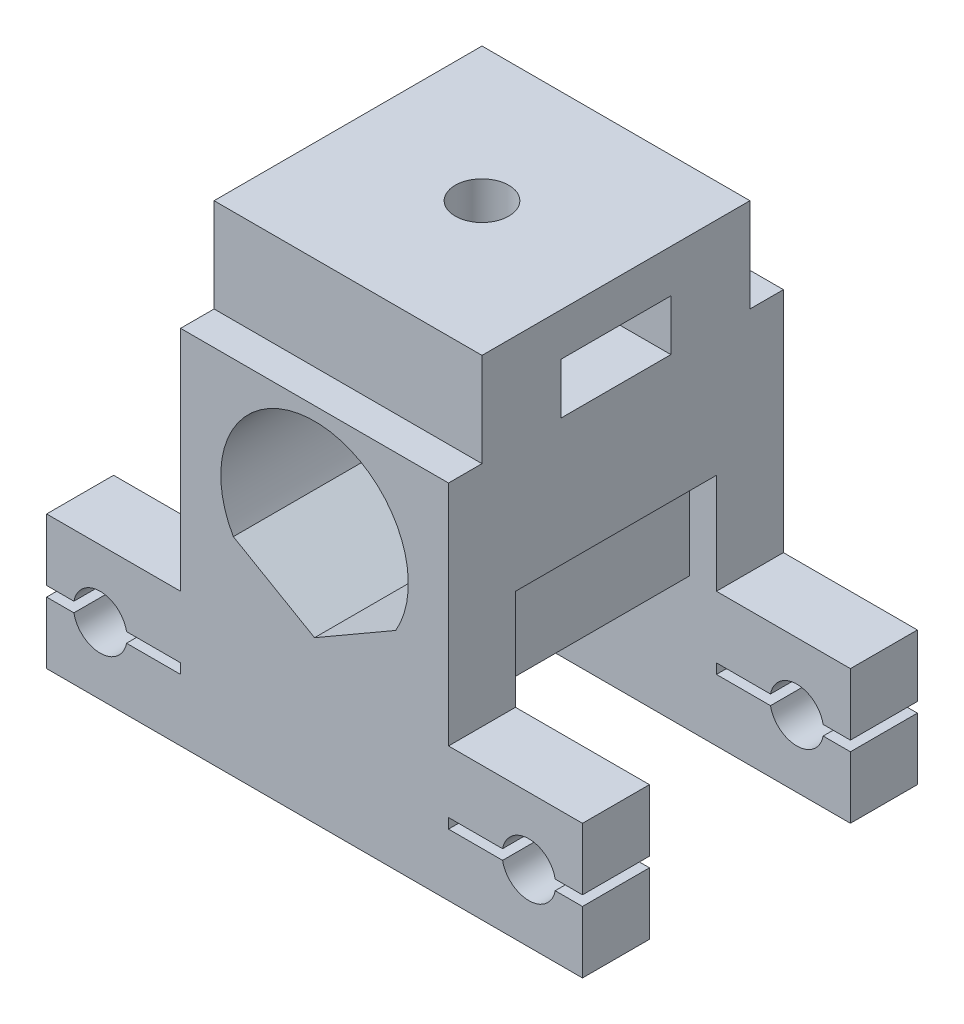
SolidWorks part; units mm, degrees
ref_plane "Front Plane" through (0, 0, 0) normal (0, 0, 1) x (1, 0, 0)
ref_plane "Top Plane" through (0, 0, 0) normal (0, 1, 0) x (1, 0, 0)
ref_plane "Right Plane" through (0, 0, 0) normal (1, 0, 0) x (0, 0, -1)
sketch "Sketch1" plane through (0, 0, 0) normal (0, 1, 0) x (1, 0, 0)
  line L1 (-10, -12.5) -> (10, -12.5)
  line L2 (-10, -12.5) -> (-10, 12.5)
  line L3 (-10, 12.5) -> (10, 12.5)
  line L4 (10, -12.5) -> (10, 12.5)
  line L5 (-10, -12.5) -> (10, 12.5) construction
  line L6 (-10, 12.5) -> (10, -12.5) construction
  point P0 (0, 0)
  dimension "D1" = 20
  dimension "D2" = 25
extrude "Boss-Extrude1" add sketch "Sketch1" along normal blind 17
sketch "Sketch2" plane through (0, 0, 12.5) normal (0, 0, 1) x (1, 0, 0)
  line L0 (0, 2) -> (-6.0622, 5.5)
  line L1 (-10, 0) -> (10, 0) construction
  line L2 (0, 2) -> (-6.4072, 2) construction
  line L3 (0, 17) -> (0, 16) construction
  line L4 (0, -55) -> (0, 55) construction
  line L5 (-10, 17) -> (10, 17) construction
  line L7 (0, 9) -> (0, 2) construction
  line L8 (0, 2) -> (6.0622, 5.5)
  arc A0 (6.0622, 5.5) -> (-6.0622, 5.5) centre (0, 9) ccw
  dimension "D1" = 2
  dimension "D2" = 3.5
  dimension "D3" = 30
extrude "Cut-Extrude1" cut sketch "Sketch2" against normal through all
ref_plane "Plane1" through (0, 0, 1.5) normal (0, 0, 1) x (1, 0, 0)
sketch "Sketch3" plane through (0, 0, 12.5) normal (0, 0, 1) x (1, 0, 0)
  line L0 (10, 0) -> (20, 0)
  line L1 (20, 0) -> (20, -10)
  line L2 (20, -10) -> (-20, -10)
  line L3 (-20, -10) -> (-20, 0)
  line L4 (-20, 0) -> (-10, 0)
  line L5 (-10, 0) -> (10, 0)
  dimension "D1" = 10
  dimension "D2" = 10
  dimension "D3" = 10
extrude "Boss-Extrude2" add sketch "Sketch3" against normal blind 5
mirror "Mirror1" about plane through (0, 0, 0) normal (0, 0, 1) of "Boss-Extrude2"
sketch "Sketch4" plane through (0, 0, 12.5) normal (0, 0, 1) x (1, 0, 0)
  line L0 (20, -10) -> (20, 0) construction
  line L1 (20, 0) -> (10, 0) construction
  line L2 (0, -13.75) -> (0, 13.75) construction
  circle A0 centre (16, -5) radius 2
  circle A1 centre (-16, -5) radius 2
  dimension "D1" = 4
  dimension "D2" = 4
  dimension "D3" = 5
extrude "Cut-Extrude2" cut sketch "Sketch4" against normal through all
sketch "Sketch6" plane through (0, 17, 0) normal (0, 1, 0) x (1, 0, 0)
  line L0 (10, -12.5) -> (10, 12.5) construction
  line L1 (-10, -10) -> (10, -10)
  line L2 (-10, -10) -> (-10, 10)
  line L3 (-10, 10) -> (10, 10)
  line L4 (10, -10) -> (10, 10)
  line L5 (-10, -10) -> (10, 10) construction
  line L6 (-10, 10) -> (10, -10) construction
  point P0 (0, 0)
  dimension "D1" = 20
extrude "Boss-Extrude3" add sketch "Sketch6" along normal blind 7 contours L2 L1 L4 L3
sketch "Sketch8" plane through (10, 0, 0) normal (1, 0, 0) x (0, 0, -1)
  line L0 (10, 17) -> (12.5, 17) construction
  line L5 (-4.1, 17) -> (4.1, 17)
  line L6 (-4.1, 17) -> (-4.1, 20.8)
  line L7 (-4.1, 20.8) -> (4.1, 20.8)
  line L8 (4.1, 17) -> (4.1, 20.8)
  line L9 (-4.1, 17) -> (4.1, 20.8) construction
  line L10 (-4.1, 20.8) -> (4.1, 17) construction
  line L11 (-10, 24) -> (-10, 17) construction
  point P0 (0, 18.9)
  dimension "D1" = 8.2
  dimension "D2" = 3.8
  dimension "D3" = 5.9
extrude "Cut-Extrude3" cut sketch "Sketch8" against normal through all
sketch "Sketch7" plane through (0, 24, 0) normal (0, 1, 0) x (1, 0, 0)
  circle A0 centre (0, 0) radius 2
extrude "Cut-Extrude4" cut sketch "Sketch7" against normal up to surface (8 mm away) up to face at (0, 10.75, 0)
sketch "Sketch9" plane through (10, 0, 0) normal (-1, 0, 0) x (0, 0, 1)
  line L0 (-12.5, 0) -> (-7.5, 0) construction
  line L1 (-7.5, 0) -> (7.5, 0)
  line L2 (-7.5, 0) -> (-7.5, 7.5)
  line L3 (-7.5, 7.5) -> (7.5, 7.5)
  line L4 (7.5, 0) -> (7.5, 7.5)
  dimension "D1" = 7.5
extrude "Cut-Extrude5" cut sketch "Sketch9" along normal blind 2
sketch "Sketch10" plane through (0, 0, 12.5) normal (0, 0, 1) x (1, 0, 0)
  line L0 (-20, 0) -> (-20, -10) construction
  line L1 (-20, -4.625) -> (-10, -4.625)
  line L2 (-20, -4.625) -> (-20, -5.375)
  line L3 (-20, -5.375) -> (-10, -5.375)
  line L4 (-10, -4.625) -> (-10, -5.375)
  line L5 (0, -0.8665) -> (0, -10) construction
  line L6 (-20, -10) -> (20, -10) construction
  line L7 (20, -4.625) -> (20, -5.375)
  line L8 (10, -4.625) -> (10, -5.375)
  line L9 (20, -5.375) -> (10, -5.375)
  line L10 (20, -4.625) -> (10, -4.625)
  circle A0 centre (-16, -5) radius 2 construction
  dimension "D1" = 0.75
  dimension "D2" = 0.375
  dimension "D3" = 10
extrude "Cut-Extrude6" cut sketch "Sketch10" against normal through all
